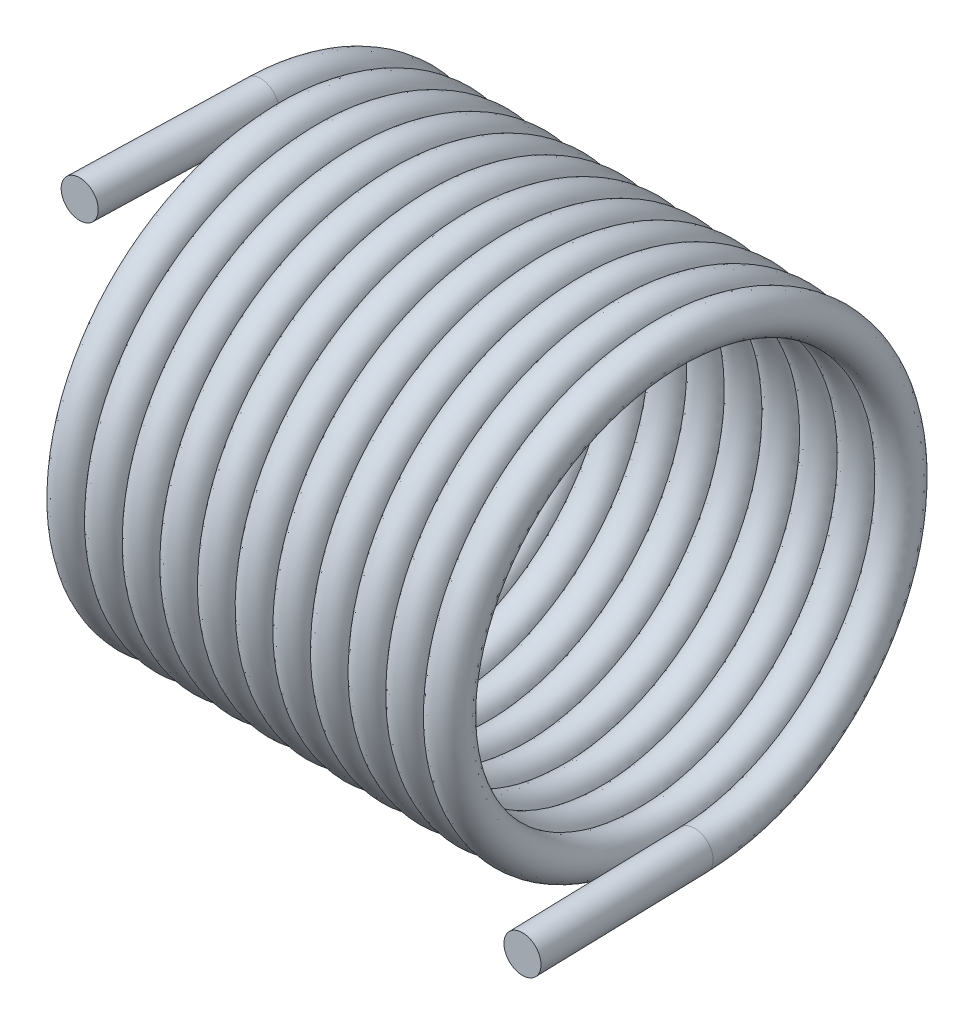
SolidWorks part; units mm, degrees
note: '?' marks a value the reader was unsure of.
ref_plane "Front" through (0, 0, 0) normal (0, 0, 1) x (1, 0, 0)
ref_plane "Top" through (0, 0, 0) normal (0, 1, 0) x (1, 0, 0)
ref_plane "Right" through (0, 0, 0) normal (1, 0, 0) x (0, 0, -1)
sketch "Sketch1" plane through (0, 0, 0) normal (1, 0, 0) x (0, 0, -1)
  line L0 (0, 0) -> (0, -8.5344) construction
  line L1 (0, -8.5344) -> (0, -9.3345) construction
  line L2 (0, -9.3345) -> (0, -10.1346) construction
  circle A0 centre (0, 0) radius 8.5344 construction
  circle A1 centre (0, 0) radius 10.1346 construction
  circle A2 centre (0, 0) radius 9.3345
  circle A3 centre (0, -9.3345) radius 0.8001 construction
  circle A4 centre (0, 0) radius 6.5532 construction
curve "Helix/Spiral1" pitch 1.6256 height 18.6944 radius 9.3345 left hand yes centre (0, 0, 0) axis (1, 0, 0) start towards (0, 1, 0)
ref_plane "Plane1" through (0, 9.3345, 0) normal (0.0277, 0, -0.9996) x (0.7745, 0.6323, 0.0215)
sketch "Sketch2" plane through (0, 9.3345, 0) normal (0.0277, 0, -0.9996) x (0.7745, 0.6323, 0.0215)
  circle A0 centre (0, 0) radius 0.8001
  dimension "D1" = 1.6002
sweep "Sweep1" add profiles "Sketch2" path "Helix/Spiral1"
sketch "Sketch3" plane through (0, 0, 0) normal (-0.0277, 0, 0.9996) x (-0.7745, -0.6323, -0.0215)
  circle A1 centre (-5.9019, -7.2319) radius 0.8001
  circle A2 centre (-5.9019, -7.2319) radius 0.8001
  dimension "D1" = 0
extrude "Extrude1" add sketch "Sketch3" along normal blind 50.8
sketch "Sketch4" plane through (0.0144, 0, 0.5178) normal (0.0277, 0, 0.9996) x (0.8176, -0.5754, -0.0227)
  circle A1 centre (20.6549, 3.1175) radius 0.8001
  circle A2 centre (20.6549, 3.1175) radius 0.8001
  dimension "D1" = 0
extrude "Extrude2" add sketch "Sketch4" along normal blind 50.8
sketch "Sketch5" plane through (0, 0, 0) normal (1, 0, 0) x (0, 0, -1)
  circle A0 centre (0, 0) radius 6.5532 construction
  circle A1 centre (0, 0) radius 6.5532
sketch "Sketch6" plane through (0, 0, 0) normal (1, 0, 0) x (0, 0, -1)
  line L1 (-53.1923, 10.1346) -> (-7.62, 10.1346)
  line L2 (-53.1923, 10.1346) -> (-53.1923, 8.5344)
  line L3 (-53.1923, 8.5344) -> (-7.62, 8.5344)
  line L4 (-7.62, 10.1346) -> (-7.62, 8.5344)
  line L5 (-50.7805, -10.1346) -> (0, -10.1346) construction
  line L6 (-7.62, -10.1346) -> (-54.272, -10.1346)
  line L7 (-7.62, -10.1346) -> (-7.62, -8.2279)
  line L8 (-7.62, -8.2279) -> (-54.272, -8.2279)
  line L10 (-50.7805, 8.5344) -> (0, 8.5344) construction
  line L11 (0, 10.1346) -> (-50.7805, 10.1346) construction
  line L12 (-54.272, -10.1346) -> (-54.272, -8.2279)
  dimension "D1" = 7.62
extrude "Cut-Extrude1" cut sketch "Sketch6" against normal through all both and the other way through all
ref_axis "Axis1" through (-2.2471, 0, 0) along (1, 0, 0)?
equation "\"D4@Helix/Spiral1\"=\"Wire Dia@Sketch1\"+.001"
equation "\"D1@Sketch2\"=\"Wire Dia@Sketch1\""
equation "\"D1@Extrude2\"=\"Leg Length@Extrude1\""
